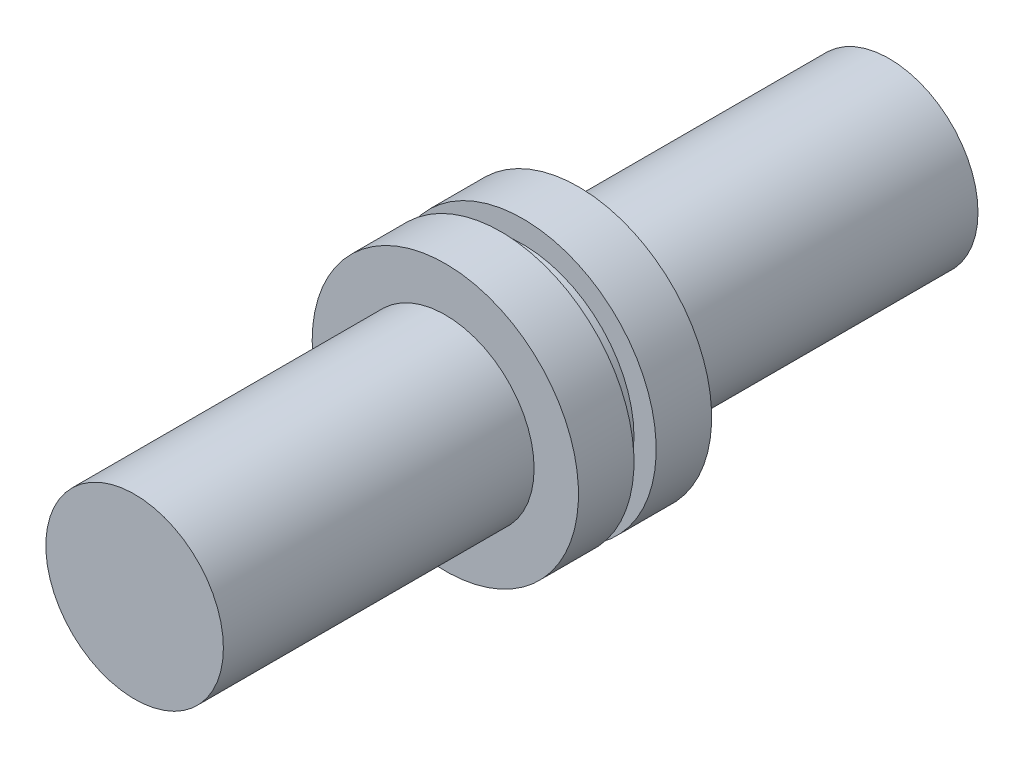
SolidWorks part; units mm, degrees
ref_plane "Front Plane" through (0, 0, 0) normal (0, 0, 1) x (1, 0, 0)
ref_plane "Top Plane" through (0, 0, 0) normal (0, 1, 0) x (1, 0, 0)
ref_plane "Right Plane" through (0, 0, 0) normal (1, 0, 0) x (0, 0, -1)
sketch "Sketch1" plane through (0, 0, 0) normal (0, 0, 1) x (1, 0, 0)
  circle A0 centre (0, 0) radius 2
  dimension "D1" = 4
extrude "Boss-Extrude1" add sketch "Sketch1" along normal blind 17
sketch3d "3DSketch2"
  circle A0 centre (0, 0, 7) radius 3
  point P2 (0, 0, 4)
  dimension "D2" = 6
  dimension "D1" = 7
extrude "Boss-Extrude2" add sketch "3DSketch2" along direction (0, 0, 1) on the side of the normal blind 3
sketch3d "3DSketch3"
  circle A0 centre (0, 0, 8.75) radius 3.429
  circle A1 centre (0, 0, 8.75) radius 2.5
  point P2 (0, 0, 12.179)
  point P6 (0, 0, 11.25)
  dimension "D2" = 5
  dimension "D1" = 1.25
extrude "Cut-Extrude1" cut sketch "3DSketch3" along direction (0, 0, 1) on the side against the normal blind 0.5
